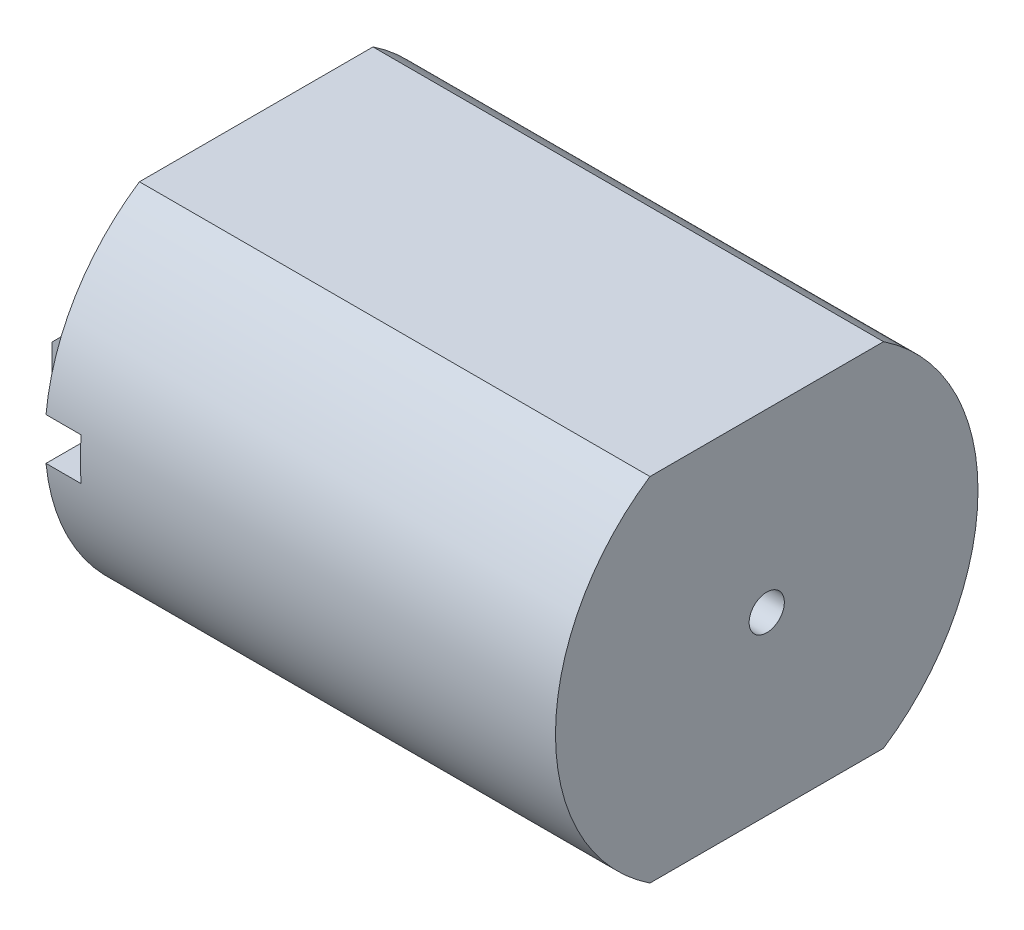
SolidWorks part; units mm, degrees
ref_plane "Alzado" through (0, 0, 0) normal (0, 0, 1) x (1, 0, 0)
ref_plane "Planta" through (0, 0, 0) normal (0, 1, 0) x (1, 0, 0)
ref_plane "Vista lateral" through (0, 0, 0) normal (1, 0, 0) x (0, 0, -1)
sketch "Croquis1" plane through (0, 0, 0) normal (1, 0, 0) x (0, 0, -1)
  line L1 (-3.3166, 5) -> (3.3166, 5)
  line L3 (-3.3166, -5) -> (3.3166, -5)
  arc A0 (-3.3166, 5) -> (-3.3166, -5) centre (0, 0) ccw
  arc A1 (3.3166, -5) -> (3.3166, 5) centre (0, 0) ccw
  dimension "D2" = 12
  dimension "D1" = 6.6332
extrude "Saliente-Extruir1" add sketch "Croquis1" along normal blind 13.5
sketch "Croquis2" plane through (0, 0, 0) normal (-1, 0, 0) x (0, 0, 1)
  line L0 (-4.9699, 0.6) -> (-4.9699, -0.6)
  line L1 (-4.9699, -0.6) -> (-5.9699, -0.6)
  line L2 (-3.3166, -5) -> (3.3166, -5)
  line L3 (3.3166, 5) -> (-3.3166, 5)
  line L4 (-3.3166, -5) -> (3.3166, -5)
  line L5 (3.3166, 5) -> (-3.3166, 5)
  line L6 (-4.9699, 0.6) -> (-5.9699, 0.6)
  line L7 (4.9699, 0.6) -> (4.9699, -0.6)
  line L8 (4.9699, -0.6) -> (5.9699, -0.6)
  line L9 (4.9699, 0.6) -> (5.9699, 0.6)
  arc A0 (-5.9699, -0.6) -> (-3.3166, -5) centre (0, 0) ccw
  arc A1 (5.9699, 0.6) -> (3.3166, 5) centre (0, 0) ccw
  arc A2 (-3.3166, 5) -> (-3.3166, -5) centre (0, 0) ccw
  arc A3 (3.3166, -5) -> (3.3166, 5) centre (0, 0) ccw
  arc A4 (-3.3166, 5) -> (-5.9699, 0.6) centre (0, 0) ccw
  arc A5 (3.3166, -5) -> (5.9699, -0.6) centre (0, 0) ccw
  point P8 (-4.9699, 0)
  point P13 (4.9699, 0)
  dimension "D2" = 1.2
  dimension "D3" = 1
  dimension "D4" = 1
  dimension "D5" = 1.2
  dimension "D1" = 0
extrude "Saliente-Extruir2" add sketch "Croquis2" along normal blind 1
sketch "Croquis3" plane through (-1, 0, 0) normal (-1, 0, 0) x (0, 0, 1)
  circle A0 centre (0, 0) radius 2.5
  circle A1 centre (0, 0) radius 0.5
  dimension "D1" = 1
  dimension "D2" = 5
extrude "Saliente-Extruir3" add sketch "Croquis3" along normal blind 1
fillet "Redondeo1" radius 0.25 1 edges at (-2, 0, 2.5)
extrude "Cortar-Extruir1" cut sketch "Croquis3<2>" against normal up to surface (14.5 mm away) contours A1 region at (-1, 0, 0) up to face at (13.5, 0, 0)
sketch "Croquis3<2>" plane through (-1, 0, 0) normal (-1, 0, 0) x (0, 0, 1) same geometry as "Croquis3"
ref_plane "Plano1" through (0, 0, 4) normal (0, 0, 1) x (1, 0, 0)
sketch "Croquis4" plane through (0, 0, 4) normal (0, 0, 1) x (1, 0, 0)
  line L1 (-2.55, 0.75) -> (-1, 0.75)
  line L2 (-2.8, 0.5) -> (-2.8, -0.5)
  line L3 (-2.55, -0.75) -> (-1, -0.75)
  line L4 (-1, 0.75) -> (-1, -0.75)
  line L5 (-2.8, 0.75) -> (-1, -0.75) construction
  line L6 (-2.8, -0.75) -> (-1, 0.75) construction
  line L7 (-1, 2.5) -> (-1, -2.5) construction
  line L8 (-2.8, 0.5) -> (-2.55, 0.75)
  line L9 (-2.8, -0.5) -> (-2.55, -0.75)
  circle A0 centre (-2.15, 0) radius 0.5
  point P0 (-1.9, 0)
  point P5 (0, 0)
  dimension "D3" = 1
  dimension "D1" = 1.5
  dimension "D2" = 1.8
  dimension "D4" = 0.25
extrude "Saliente-Extruir4" add sketch "Croquis4" against normal blind 0.25
pattern_linear "MatrizL1" count 2 spacing 8 along (0, 0, -1) of "Saliente-Extruir4"
